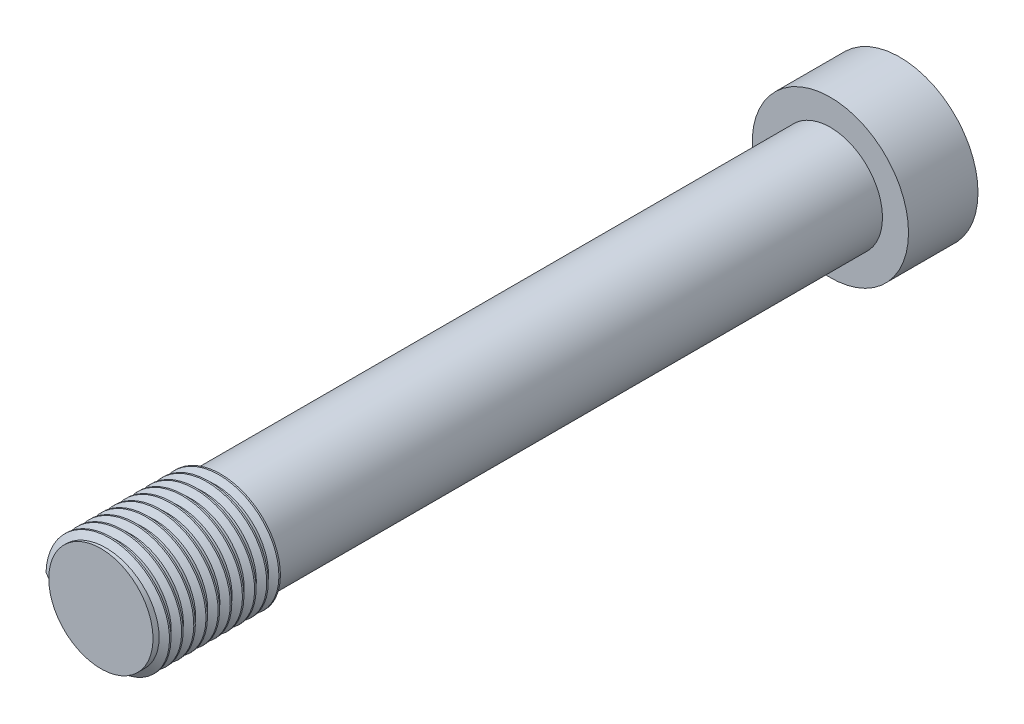
SolidWorks part; units mm, degrees
ref_plane "Front Plane" through (0, 0, 0) normal (0, 0, 1) x (1, 0, 0)
ref_plane "Top Plane" through (0, 0, 0) normal (0, 1, 0) x (1, 0, 0)
ref_plane "Right Plane" through (0, 0, 0) normal (1, 0, 0) x (0, 0, -1)
sketch "Sketch1" plane through (0, 0, 0) normal (0, 0, 1) x (1, 0, 0)
  circle A0 centre (0, 0) radius 22.5
extrude "Boss-Extrude1" add sketch "Sketch1" along normal blind 20
sketch "Sketch2" plane through (0, 0, 20) normal (0, 0, 1) x (1, 0, 0)
  circle A0 centre (0, 0) radius 15
extrude "Boss-Extrude2" add sketch "Sketch2" along normal blind 210
thread "Thread1" pitch 3.5 method extrude profile "Thread Profile1" start angle 0, offset 0, length 35, pitch 3.5, diameter 30
ref_plane "Plane1" through (-15, 0, 230) normal (0, -1, 0) x (-1, 0, 0)
sketch "Thread Profile1" plane through (-15, 0, 230) normal (0, -1, 0) x (-1, 0, 0)
  line L0 (0, 0) -> (0, 3.5) construction
  line L1 (0, 0) -> (1.8944, 1.0937)
  line L2 (1.8944, 1.0937) -> (1.8944, 1.5312)
  line L3 (1.8944, 1.5312) -> (0, 2.625)
  line L4 (1.8944, 1.3125) -> (0, 1.3125) construction
  line L11 (0, 0) -> (0, 2.625)
  point P2 (0, 0)
  dimension "Pitch" = 3.5
  dimension "Profile_Angle" = 60
  dimension "Profile_Land" = 0.4375
  dimension "Profile_Height" = 1.8944
